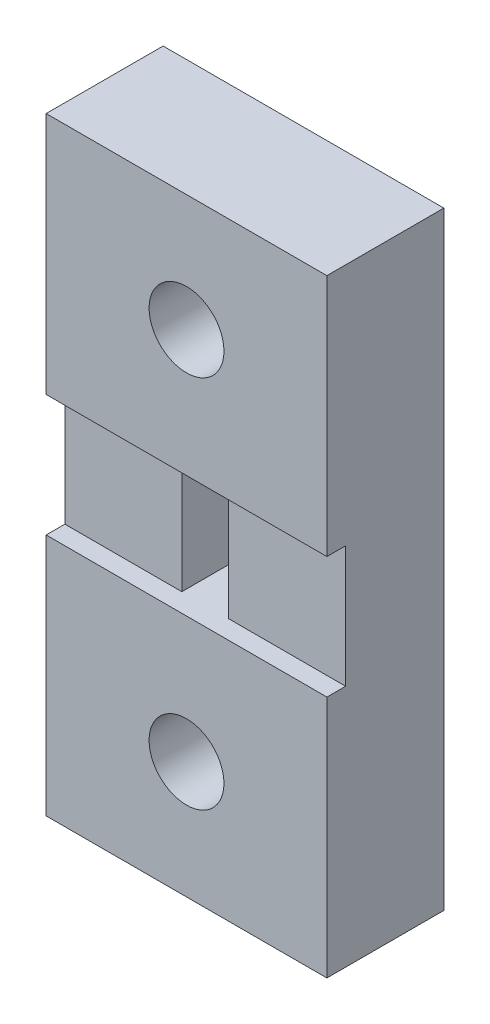
SolidWorks part; units mm, degrees
ref_plane "Front Plane" through (0, 0, 0) normal (0, 0, 1) x (1, 0, 0)
ref_plane "Top Plane" through (0, 0, 0) normal (0, 1, 0) x (1, 0, 0)
ref_plane "Right Plane" through (0, 0, 0) normal (1, 0, 0) x (0, 0, -1)
sketch "Sketch1" plane through (0, 0, 0) normal (0, 0, 1) x (1, 0, 0)
  line L0 (0, -8) -> (0, 8)
  line L1 (6, -13) -> (-6, -13)
  line L2 (6, -13) -> (6, 13)
  line L3 (6, 13) -> (-6, 13)
  line L4 (-6, -13) -> (-6, 13)
  line L5 (6, -13) -> (-6, 13) construction
  line L6 (6, 13) -> (-6, -13) construction
  line L8 (-1, -2.6) -> (1, -2.6)
  line L9 (-1, -2.6) -> (-1, 2.6)
  line L10 (-1, 2.6) -> (1, 2.6)
  line L11 (1, -2.6) -> (1, 2.6)
  line L12 (-1, -2.6) -> (1, 2.6) construction
  line L13 (-1, 2.6) -> (1, -2.6) construction
  circle A0 centre (0, 8) radius 1.6
  circle A1 centre (0, -8) radius 1.6
  point P0 (0, 0)
  point P9 (0, 0)
  point P11 (0, 0)
  dimension "D4" = 3.2
  dimension "D5" = 3.2
  dimension "D1" = 26
  dimension "D2" = 12
  dimension "D3" = 16
  dimension "D6" = 5.2
  dimension "D7" = 2
extrude "Boss-Extrude1" add sketch "Sketch1" along normal blind 5 contours L4 L1 L2 L3 A1 L8 L9 L10 A0 L11 region at (0, -12.7136, 0)
sketch "Sketch3" plane through (0, 0, 5) normal (0, 0, 1) x (1, 0, 0)
  line L0 (6, -13) -> (6, 13) construction
  line L1 (-6, -2.6) -> (6, -2.6)
  line L2 (-6, -2.6) -> (-6, 2.6)
  line L3 (-6, 2.6) -> (6, 2.6)
  line L4 (6, -2.6) -> (6, 2.6)
  line L5 (-6, -2.6) -> (6, 2.6) construction
  line L6 (-6, 2.6) -> (6, -2.6) construction
  line L7 (-1, 2.6) -> (1, 2.6) construction
  point P0 (0, 0)
extrude "Cut-Extrude1" cut sketch "Sketch3" against normal blind 0.8
sketch "Sketch4" plane through (0, 0, 0) normal (0, 0, -1) x (-1, 0, 0)
  line L0 (-6, -13) -> (6, -13) construction
  line L1 (1.7321, 11) -> (-1.7321, 11)
  line L2 (-1.7321, 11) -> (-3.4641, 8)
  line L3 (-3.4641, 8) -> (-1.7321, 5)
  line L4 (-1.7321, 5) -> (1.7321, 5)
  line L5 (1.7321, 5) -> (3.4641, 8)
  line L6 (3.4641, 8) -> (1.7321, 11)
  line L7 (1.7321, -5) -> (-1.7321, -5)
  line L8 (-1.7321, -5) -> (-3.4641, -8)
  line L9 (-3.4641, -8) -> (-1.7321, -11)
  line L10 (-1.7321, -11) -> (1.7321, -11)
  line L11 (1.7321, -11) -> (3.4641, -8)
  line L12 (3.4641, -8) -> (1.7321, -5)
  circle A0 centre (0, 8) radius 3 construction
  circle A1 centre (0, -8) radius 3 construction
  dimension "D2" = 6
  dimension "D1" = 6
extrude "Cut-Extrude2" cut sketch "Sketch4" against normal blind 2.5
